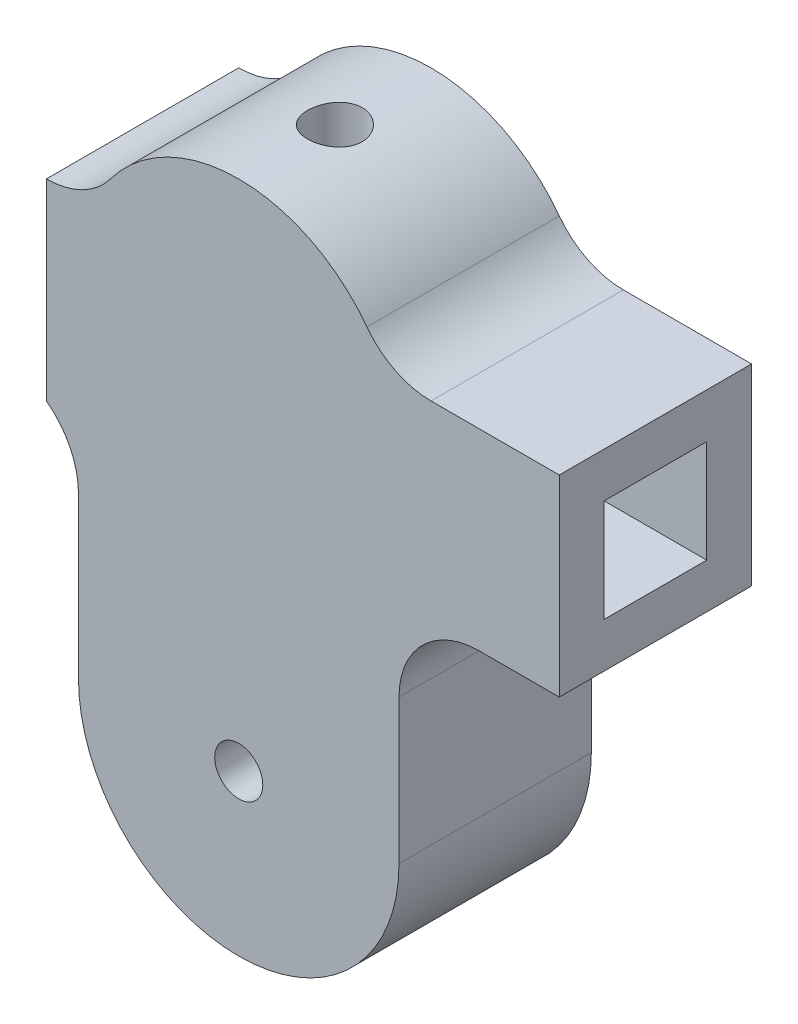
SolidWorks part; units mm, degrees
material "ABS"
ref_plane "Front Plane" through (0, 0, 0) normal (0, 0, 1) x (1, 0, 0)
ref_plane "Top Plane" through (0, 0, 0) normal (0, 1, 0) x (1, 0, 0)
ref_plane "Right Plane" through (0, 0, 0) normal (1, 0, 0) x (0, 0, -1)
sketch "Sketch1" plane through (0, 0, 0) normal (0, 0, 1) x (1, 0, 0)
  line L0 (0, 22) -> (0, 0) construction
  line L1 (10, 22) -> (10, 0)
  line L2 (-10, 22) -> (-10, 0)
  arc A1 (10, 22) -> (-10, 22) centre (0, 22) ccw
  arc A2 (-10, 0) -> (10, 0) centre (0, 0) ccw
  point P3 (0, 11)
  point P9 (0, 32)
  point P10 (0, -10)
  dimension "D1" = 20
  dimension "D2" = 42
sketch "Sketch2" plane through (0, 0, 0) normal (0, 0, 1) x (1, 0, 0)
  line L0 (0, 0) -> (0, 32) construction
  line L1 (-2.5, 19.7394) -> (-4.37, 0.2091)
  line L2 (2.5, 19.7394) -> (4.37, 0.2091)
  line L3 (-10, 0) -> (10, 0) construction
  line L8 (-10, 22) -> (-10, 0) construction
  line L9 (10, 22) -> (10, 0) construction
  arc A0 (-4.37, 0.2091) -> (4.37, -0.2091) centre (0, 0) ccw
  arc A2 (-2.5, 19.7394) -> (2.5, 19.7394) centre (0, 19.5) cw
  arc A3 (4.37, -0.2091) -> (4.37, 0.2091) centre (0, 0) ccw
  arc A5 (10, 22) -> (-10, 22) centre (0, 22) ccw construction
  dimension "D1" = 4.375
  dimension "D2" = 8.74
  dimension "D3" = 19.5
  dimension "D4" = 5
extrude "Boss-Extrude1" add sketch "Sketch1" along normal blind 12
sketch "Sketch4" plane through (0, 0, 0) normal (0, 0, 1) x (1, 0, 0)
  circle A0 centre (0, 0) radius 1.5
  dimension "D1" = 3
extrude "Cut-Extrude2" cut sketch "Sketch4" along normal through all
sketch "Sketch7" plane through (0, 0, 0) normal (1, 0, 0) x (0, 0, -1)
  line L0 (-12, 32) -> (-12, 22) construction
  line L1 (0, 14) -> (-12, 14)
  line L2 (0, 14) -> (0, 26)
  line L3 (0, 26) -> (-12, 26)
  line L4 (-12, 14) -> (-12, 26)
  line L5 (0, 0) -> (0, 22) construction
  point P7 (0, 20)
  point P9 (0, 0)
  dimension "D1" = 20
extrude "Boss-Extrude2" add sketch "Sketch7" along normal blind 20 and the other way blind 12
extrude "Cut-Extrude1" cut sketch "Sketch2" along normal blind 2
ref_axis "Axis1" through (0, 0, 0) along (0, 0, 1)
sketch "Sketch8" plane through (20, 0, 0) normal (1, 0, 0) x (0, 0, -1)
  line L0 (-12, 14) -> (0, 14) construction
  line L1 (-9.2, 23.2) -> (-2.8, 23.2)
  line L2 (-9.2, 23.2) -> (-9.2, 16.8)
  line L3 (-9.2, 16.8) -> (-2.8, 16.8)
  line L4 (-2.8, 23.2) -> (-2.8, 16.8)
  line L5 (-9.2, 23.2) -> (-2.8, 16.8) construction
  line L6 (-9.2, 16.8) -> (-2.8, 23.2) construction
  line L7 (0, 20) -> (-12, 20) construction
  line L8 (0, 14) -> (0, 26) construction
  line L9 (-12, 26) -> (-12, 14) construction
  line L10 (-6, 14) -> (-6, 26) construction
  line L11 (0, 26) -> (-12, 26) construction
  point P0 (-6, 20)
  point P18 (-6, 20)
  dimension "D1" = 6.4
extrude "Cut-Extrude4" cut sketch "Sketch8" against normal through all
sketch "Sketch9" plane through (0, 0, 0) normal (0, 0, -1) x (-1, 0, 0)
  line L1 (-2.8, 27.8) -> (2.8, 27.8)
  line L2 (-2.8, 27.8) -> (-2.8, 24.7)
  line L3 (-2.8, 24.7) -> (2.8, 24.7)
  line L4 (2.8, 27.8) -> (2.8, 24.7)
  line L5 (-2.8, 27.8) -> (2.8, 24.7) construction
  line L6 (-2.8, 24.7) -> (2.8, 27.8) construction
  line L7 (12, 23.2) -> (-20, 23.2) construction
  point P0 (0, 26.25)
  dimension "D1" = 3.1
  dimension "D2" = 5.6
  dimension "D3" = 1.5
extrude "Cut-Extrude5" cut sketch "Sketch9" against normal blind 9
sketch "Sketch10" plane through (0, 23.2, 0) normal (0, -1, 0) x (1, 0, 0)
  line L1 (0, 12) -> (0, 0) construction
  line L2 (10, 12) -> (-10, 12) construction
  circle A0 centre (0, 6) radius 1.7
  point P10 (0, 6)
  dimension "D1" = 3.4
extrude "Cut-Extrude6" cut sketch "Sketch10" against normal through all
fillet "Fillet1" radius 5 4 edges at (10, 14, 6) (9.1652, 26, 6) (-10, 14, 6) (-9.1652, 26, 6)
